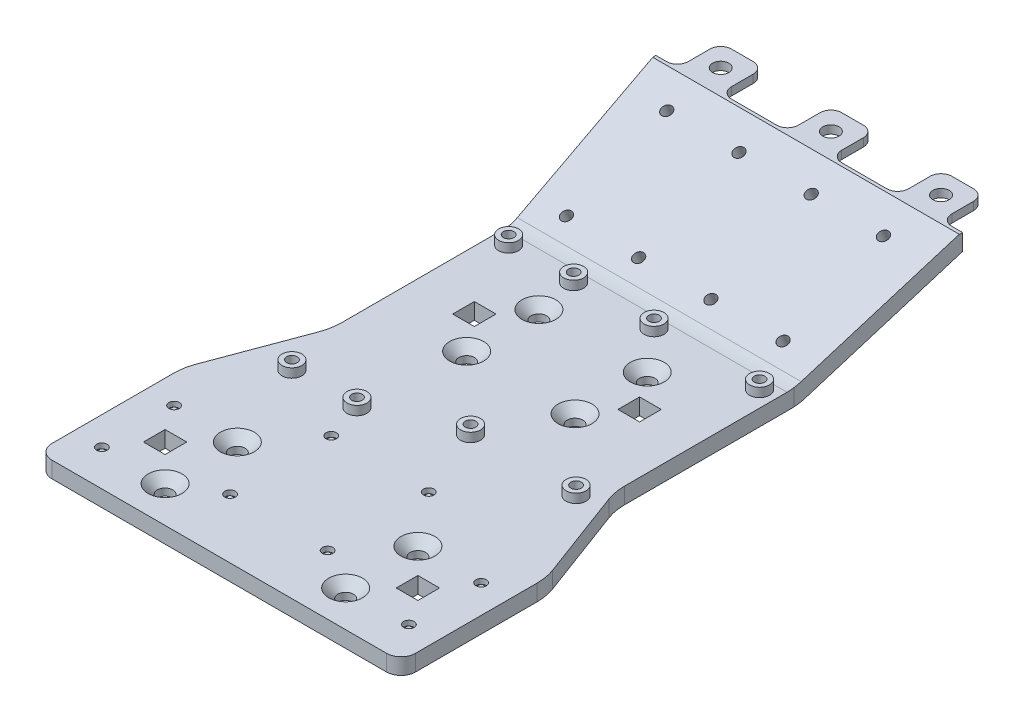
SolidWorks part; units mm, degrees
material "Onyx w/ CF"
ref_plane "Front Plane" through (0, 0, 0) normal (0, 0, 1) x (1, 0, 0)
ref_plane "Top Plane" through (0, 0, 0) normal (0, 1, 0) x (1, 0, 0)
ref_plane "Right Plane" through (0, 0, 0) normal (1, 0, 0) x (0, 0, -1)
sketch "Sketch1" plane through (0, 0, 0) normal (0, 1, 0) x (1, 0, 0)
  line L0 (-39.17, 0) -> (39.17, 0)
  line L3 (-50.325, -79.6) -> (-50.325, -120)
  line L5 (50.325, -120) -> (50.325, -79.6)
  line L8 (-50.325, -120) -> (50.325, -120)
  line L9 (39.17, 0) -> (39.17, -49.7)
  line L10 (-39.17, 0) -> (-39.17, -49.7)
  line L11 (39.17, -49.7) -> (50.325, -79.6)
  line L12 (-50.325, -79.6) -> (-39.17, -49.7)
  point P1 (0, -120)
  point P4 (0, 0)
  dimension "D1" = 78.34
  dimension "D2" = 40.4
  dimension "D3" = 120
  dimension "D4" = 49.7
  dimension "D5" = 100.65
extrude "Boss-Extrude1" add sketch "Sketch1" along normal mid plane 4.5
sketch "Sketch5" plane through (0, 2.25, 0) normal (0, 1, 0) x (1, 0, 0)
  line L3 (-22.875, -26.5) -> (22.875, -26.5) construction
  line L6 (39.17, 0) -> (-39.17, 0) construction
  line L9 (-35, -100) -> (35, -100) construction
  line L19 (-25.875, -23.5) -> (-19.875, -23.5)
  line L20 (-25.875, -23.5) -> (-25.875, -29.5)
  line L21 (-25.875, -29.5) -> (-19.875, -29.5)
  line L22 (-19.875, -23.5) -> (-19.875, -29.5)
  line L23 (-25.875, -23.5) -> (-19.875, -29.5) construction
  line L24 (-25.875, -29.5) -> (-19.875, -23.5) construction
  line L25 (19.875, -23.5) -> (25.875, -23.5)
  line L26 (19.875, -23.5) -> (19.875, -29.5)
  line L27 (19.875, -29.5) -> (25.875, -29.5)
  line L28 (25.875, -23.5) -> (25.875, -29.5)
  line L29 (19.875, -23.5) -> (25.875, -29.5) construction
  line L30 (19.875, -29.5) -> (25.875, -23.5) construction
  line L37 (-50.325, -120) -> (50.325, -120) construction
  line L44 (-38, -97) -> (-32, -97)
  line L45 (-38, -97) -> (-38, -103)
  line L46 (-38, -103) -> (-32, -103)
  line L47 (-32, -97) -> (-32, -103)
  line L48 (-38, -97) -> (-32, -103) construction
  line L49 (-38, -103) -> (-32, -97) construction
  line L50 (32, -97) -> (38, -97)
  line L51 (32, -97) -> (32, -103)
  line L52 (32, -103) -> (38, -103)
  line L53 (38, -97) -> (38, -103)
  line L54 (32, -97) -> (38, -103) construction
  line L55 (32, -103) -> (38, -97) construction
  point P4 (0, -26.5)
  point P5 (0, -100)
  dimension "D1" = 26.5
  dimension "D2" = 45.75
  dimension "D3" = 6
  dimension "D4" = 70
  dimension "D7" = 20
extrude "Cut-Extrude1" cut sketch "Sketch5" against normal through all
hole_wizard "CSK for M4 Flat Head Machine Screw1" positions "Sketch6" profile "Sketch7" countersink size "M4" standard "ANSI Metric" end condition through all
sketch "Sketch6" plane through (0, 2.25, 0) normal (0, -1, 0) x (-1, 0, 0)
  line L1 (-15, -16.5) -> (15, -16.5)
  line L2 (-15, -16.5) -> (-15, -36.5)
  line L3 (-15, -36.5) -> (15, -36.5)
  line L4 (15, -16.5) -> (15, -36.5)
  line L5 (-15, -16.5) -> (15, -36.5) construction
  line L6 (-15, -36.5) -> (15, -16.5) construction
  line L7 (-39.17, 0) -> (39.17, 0) construction
  line L9 (-25, -90) -> (25, -90)
  line L10 (-25, -90) -> (-25, -110)
  line L11 (-25, -110) -> (25, -110)
  line L12 (25, -90) -> (25, -110)
  line L13 (-25, -90) -> (25, -110) construction
  line L14 (-25, -110) -> (25, -90) construction
  line L15 (50.325, -120) -> (-50.325, -120) construction
  point P0 (-15, -16.5)
  point P3 (15, -16.5)
  point P6 (15, -36.5)
  point P8 (-15, -36.5)
  point P49 (0, -36.5)
  point P66 (25, -110)
  point P69 (-25, -90)
  point P70 (-25, -110)
  point P71 (25, -90)
  point P96 (0, -90)
  dimension "D1" = 16.5
  dimension "D2" = 20
  dimension "D3" = 30
  dimension "D4" = 20
  dimension "D5" = 50
  dimension "D6" = 10
sketch "Sketch7" plane through (15, 2.25, 16.5) normal (1, 0, 0) x (0, 0, 1)
  line L0 (0, 0) -> (0, 4.5)
  line L1 (0, 4.5) -> (2.15, 4.5)
  line L2 (2.15, 4.5) -> (2.15, 2.55)
  line L3 (2.15, 2.55) -> (4.7, 0)
  line L5 (4.7, 0) -> (0, 0)
  line L6 (-2.15, 2.55) -> (-4.7, 0) construction
  line L11 (0, -6.35) -> (0, 107.95) construction
  dimension "Thru Hole Dia." = 4.3
  dimension "Thru Hole Depth" = 4.5
  dimension "Near C'Sink Dia." = 9.4
  dimension "Near C'Sink Angle" = 90
fillet "Fillet2" radius 4 2 edges at (-50.325, 0, 120) (50.325, 0, 120)
fillet "Fillet3" radius 15 4 edges at (50.325, 0, 79.6) (39.17, 0, 49.7) (-50.325, 0, 79.6) (-39.17, 0, 49.7)
sketch "Sketch18" plane through (0, 0, 0) normal (1, 0, 0) x (0, 0, -1)
  line L0 (0, 2.25) -> (42.4584, 19.55)
  line L1 (42.4584, 19.55) -> (43.34, 19.55)
  line L2 (43.34, 19.55) -> (43.34, 15.05)
  line L3 (43.34, 15.05) -> (0.8816, -2.25)
  line L4 (0.8816, -2.25) -> (0, -2.25)
  line L5 (0, 2.25) -> (0, -2.25) construction
  line L6 (0, 2.25) -> (0, -2.25)
  dimension "D1" = 43.34
  dimension "D2" = 17.3
  dimension "D3" = 4.5
extrude "Boss-Extrude2" add sketch "Sketch18" against normal mid plane 85
sketch "Sketch21" plane through (0, -2.25, 0) normal (0, -1, 0) x (1, 0, 0)
  line L0 (39.17, 0) -> (42.5, -43.34)
  line L1 (42.5, -43.34) -> (42.5, 0)
  line L2 (42.5, 0) -> (39.17, 0)
  line L3 (39.17, 0) -> (42.5, 0) construction
  line L4 (0, -11.99) -> (0, 11.99) construction
  line L5 (-42.5, 0) -> (-39.17, 0)
  line L6 (-42.5, -43.34) -> (-42.5, 0)
  line L7 (-39.17, 0) -> (-42.5, -43.34)
extrude "Cut-Extrude5" cut sketch "Sketch21" against normal through all
fillet "Fillet5" radius 10 2 edges at (0, 2.25, 0) (0, -2.25, -0.8816)
sketch "Sketch22" plane through (0, 19.55, 0) normal (0, 1, 0) x (1, 0, 0)
  line L0 (-42.5, 43.34) -> (42.5, 43.34) construction
  line L1 (-36.5, 43.34) -> (-24.5, 43.34)
  line L2 (-36.5, 43.34) -> (-36.5, 55.34)
  line L3 (-36.5, 55.34) -> (-24.5, 55.34)
  line L4 (-24.5, 43.34) -> (-24.5, 55.34)
  line L5 (-32.5, 49.34) -> (-36.5, 49.34) construction
  line L6 (6, 43.34) -> (-6, 43.34)
  line L7 (6, 43.34) -> (6, 55.34)
  line L8 (6, 55.34) -> (-6, 55.34)
  line L9 (-6, 43.34) -> (-6, 55.34)
  line L10 (6, 43.34) -> (-6, 55.34) construction
  line L11 (6, 55.34) -> (-6, 43.34) construction
  line L12 (-30.5, 51.34) -> (-30.5, 55.34) construction
  line L13 (0, -11.99) -> (0, 11.99) construction
  line L14 (36.5, 55.34) -> (24.5, 55.34)
  line L15 (24.5, 43.34) -> (24.5, 55.34)
  line L16 (36.5, 43.34) -> (24.5, 43.34)
  line L17 (36.5, 43.34) -> (36.5, 55.34)
  circle A0 centre (-30.5, 49.34) radius 2 construction
  point P6 (0, 49.34)
  point P11 (0, 43.34)
  point P12 (-30.5, 55.34)
  point P17 (-24.5, 49.34)
  dimension "D2" = 4
  dimension "D1" = 12
  dimension "D3" = 4
extrude "Boss-Extrude3" add sketch "Sketch22" against normal blind 2.25
fillet "Fillet6" radius 3 12 edges at (-36.5, 18.425, -55.34) (-36.5, 18.425, -43.34) (-24.5, 18.425, -55.34) (-24.5, 18.425, -43.34) (-6, 18.425, -43.34) (-6, 18.425, -55.34) (6, 18.425, -55.34) (6, 18.425, -43.34) (24.5, 18.425, -43.34) (36.5, 18.425, -43.34) (36.5, 18.425, -55.34) (24.5, 18.425, -55.34)
hole_wizard "M4 Clearance Hole1" positions "Sketch23" profile "Sketch24" hole size "M4" standard "ANSI Metric" end condition through all
sketch "Sketch23" plane through (0, 19.55, 0) normal (0, 1, 0) x (1, 0, 0)
  line L0 (-27.5, 55.34) -> (-33.5, 55.34) construction
  line L1 (-24.5, 46.34) -> (-24.5, 52.34) construction
  line L2 (33.5, 55.34) -> (27.5, 55.34) construction
  line L3 (3, 55.34) -> (-3, 55.34) construction
  point P0 (30.5, 49.34)
  point P2 (0, 49.34)
  point P4 (-30.5, 49.34)
  point P9 (-30.5, 55.34)
  point P12 (-24.5, 49.34)
  point P17 (30.5, 55.34)
  point P20 (0, 55.34)
sketch "Sketch24" plane through (30.5, 19.55, -49.34) normal (1, 0, 0) x (0, 0, 1)
  line L0 (0, 0) -> (0, 21.8)
  line L1 (0, 21.8) -> (2.25, 21.8)
  line L2 (2.25, 21.8) -> (2.25, 0)
  line L5 (2.25, 0) -> (0, 0)
  line L11 (0, -6.35) -> (0, 107.95) construction
  dimension "Thru Hole Dia." = 4.5
  dimension "Thru Hole Depth" = 21.8
hole_wizard "M2.5 Clearance Hole2" positions "Sketch29" profile "Sketch30" hole size "M2.5" standard "ANSI Metric" end condition through all
sketch "Sketch29" plane through (0, 1.9296, 0.7862) normal (0, 0.9261, 0.3773) x (1, 0, 0)
  line L3 (0, 46.6967) -> (0, 0) construction
  line L4 (-42.4323, 46.6967) -> (42.4323, 46.6967) construction
  line L6 (9.17, 38.3483) -> (9.17, 8.3483) construction
  point P0 (29.17, 38.3483)
  point P2 (9.17, 38.3483)
  point P4 (-10.83, 38.3483)
  point P6 (-30.83, 38.3483)
  point P11 (29.17, 8.3483)
  point P13 (9.17, 8.3483)
  point P15 (-10.83, 8.3483)
  point P17 (-30.83, 8.3483)
  point P42 (0, 23.3483)
  point P43 (9.17, 23.3483)
  dimension "D1" = 10
  dimension "D2" = 20
  dimension "D3" = 20
  dimension "D4" = 20
  dimension "D5" = 30
sketch "Sketch30" plane through (29.17, 16.3999, -34.7272) normal (1, 0, 0) x (0, -0.3773, 0.9261)
  line L0 (0, 0) -> (0, 25.0492)
  line L1 (0, 25.0492) -> (1.45, 25.0492)
  line L2 (1.45, 25.0492) -> (1.45, 0)
  line L5 (1.45, 0) -> (0, 0)
  line L11 (0, -6.35) -> (0, 107.95) construction
  dimension "Thru Hole Dia." = 2.9
  dimension "Thru Hole Depth" = 25.0492
sketch "Sketch31" plane through (0, 2.25, 0) normal (0, 1, 0) x (1, 0, 0)
  line L0 (39.17, -1.9591) -> (-39.17, -1.9591) construction
  line L1 (1.07, -1.9591) -> (39.17, -1.9591) construction
  line L2 (1.07, -1.9591) -> (1.07, -59.1091) construction
  line L3 (1.07, -59.1091) -> (39.17, -59.1091) construction
  line L4 (39.17, -1.9591) -> (39.17, -59.1091) construction
  line L5 (39.17, -46.993) -> (39.17, -1.9591) construction
  line L6 (34.725, -5.1341) -> (5.515, -5.1341) construction
  line L7 (34.725, -5.1341) -> (34.725, -55.9341) construction
  line L9 (-16.67, -5.2091) -> (-16.67, -65.2091) construction
  line L10 (-16.67, -65.2091) -> (-34.67, -65.2091) construction
  line L11 (-34.67, -65.2091) -> (-34.67, -5.2091) construction
  line L12 (-34.67, -5.2091) -> (-16.67, -5.2091) construction
  line L13 (-39.17, -1.9591) -> (-39.17, -46.993) construction
  circle A0 centre (34.725, -5.1341) radius 2.75
  circle A1 centre (5.515, -5.1341) radius 2.75
  circle A2 centre (5.515, -55.9341) radius 2.75
  circle A3 centre (34.725, -55.9341) radius 2.75
  circle A4 centre (34.725, -5.1341) radius 1.25 construction
  circle A5 centre (-16.67, -5.2091) radius 2.75
  circle A6 centre (-34.67, -5.2091) radius 2.75
  circle A7 centre (-34.67, -65.2091) radius 2.75
  circle A8 centre (-16.67, -65.2091) radius 2.75
  point P16 (20.12, -1.9591)
  point P17 (20.12, -5.1341)
  point P18 (34.725, -30.5341)
  point P19 (39.17, -30.5341)
  dimension "D3" = 3.175
  dimension "D5" = 2.5
  dimension "D6" = 5.5
  dimension "D7" = 4.5
  dimension "D11" = 5.5
  dimension "D1" = 38.1
  dimension "D2" = 57.15
  dimension "D4" = 29.21
  dimension "D8" = 3.25
  dimension "D9" = 60
  dimension "D10" = 18
extrude "Boss-Extrude4" add sketch "Sketch31" along normal blind 2.5
hole_wizard "M2.5 Clearance Hole3" positions "Sketch32" profile "Sketch33" hole size "M2.5" standard "ANSI Metric" end condition through all
sketch "Sketch32" plane through (0, 4.75, 0) normal (0, 1, 0) x (1, 0, 0)
  line L1 (13.5, -75.5) -> (-13.5, -75.5)
  line L2 (13.5, -75.5) -> (13.5, -103.5)
  line L3 (13.5, -103.5) -> (-13.5, -103.5)
  line L4 (-13.5, -75.5) -> (-13.5, -103.5)
  line L5 (-46.325, -120) -> (46.325, -120) construction
  line L6 (42.5, -90) -> (42.5, -110)
  line L8 (-42.5, -90) -> (-42.5, -110)
  line L10 (42.5, -100) -> (-42.5, -100) construction
  circle A0 centre (34.725, -5.1341) radius 2.75 construction
  circle A1 centre (34.725, -55.9341) radius 2.75 construction
  circle A2 centre (5.515, -5.1341) radius 2.75 construction
  circle A3 centre (5.515, -55.9341) radius 2.75 construction
  circle A4 centre (-16.67, -5.2091) radius 2.75 construction
  circle A5 centre (-16.67, -65.2091) radius 2.75 construction
  circle A6 centre (-34.67, -5.2091) radius 2.75 construction
  circle A7 centre (-34.67, -65.2091) radius 2.75 construction
  point P0 (34.725, -5.1341)
  point P2 (34.725, -55.9341)
  point P4 (5.515, -55.9341)
  point P6 (5.515, -5.1341)
  point P8 (-16.67, -5.2091)
  point P10 (-16.67, -65.2091)
  point P12 (-34.67, -65.2091)
  point P14 (-34.67, -5.2091)
  point P42 (13.5, -75.5)
  point P43 (-13.5, -103.5)
  point P46 (13.5, -103.5)
  point P47 (-13.5, -75.5)
  point P71 (0, -75.5)
  point P88 (-42.5, -90)
  point P90 (-42.5, -110)
  point P92 (42.5, -90)
  point P94 (42.5, -110)
  point P109 (0, -100)
  point P110 (0, -103.5)
  dimension "D1" = 16.5
  dimension "D2" = 28
  dimension "D3" = 27
  dimension "D4" = 85
  dimension "D5" = 20
  dimension "D6" = 20
sketch "Sketch33" plane through (34.725, 4.75, 5.1341) normal (1, 0, 0) x (0, 0, 1)
  line L0 (0, 0) -> (0, 7)
  line L1 (0, 7) -> (1.45, 7)
  line L2 (1.45, 7) -> (1.45, 0)
  line L5 (1.45, 0) -> (0, 0)
  line L11 (0, -6.35) -> (0, 107.95) construction
  dimension "Thru Hole Dia." = 2.9
  dimension "Thru Hole Depth" = 7
sketch "Sketch34" plane through (0, 0, 0) normal (0, 1, 0) x (1, 0, 0)
  line L0 (37.5774, -2.2817) -> (37.5774, -7.9865)
  line L1 (8.215, -2.4341) -> (2.815, -2.4341) construction
  line L2 (8.215, -2.4341) -> (8.215, -7.8341) construction
  line L3 (8.215, -7.8341) -> (2.815, -7.8341) construction
  line L4 (2.815, -2.4341) -> (2.815, -7.8341) construction
  line L5 (8.215, -2.4341) -> (2.815, -7.8341) construction
  line L6 (8.215, -7.8341) -> (2.815, -2.4341) construction
  line L7 (8.215, -53.2341) -> (2.815, -53.2341) construction
  line L8 (8.215, -53.2341) -> (8.215, -58.6341) construction
  line L9 (8.215, -58.6341) -> (2.815, -58.6341) construction
  line L10 (2.815, -53.2341) -> (2.815, -58.6341) construction
  line L11 (8.215, -53.2341) -> (2.815, -58.6341) construction
  line L12 (8.215, -58.6341) -> (2.815, -53.2341) construction
  line L13 (37.425, -53.2341) -> (32.025, -53.2341) construction
  line L14 (37.425, -53.2341) -> (37.425, -58.6341) construction
  line L15 (37.425, -58.6341) -> (32.025, -58.6341) construction
  line L16 (32.025, -53.2341) -> (32.025, -58.6341) construction
  line L17 (37.425, -53.2341) -> (32.025, -58.6341) construction
  line L18 (37.425, -58.6341) -> (32.025, -53.2341) construction
  line L19 (37.425, -2.4341) -> (32.025, -2.4341) construction
  line L20 (37.425, -2.4341) -> (37.425, -7.8341) construction
  line L21 (37.425, -7.8341) -> (32.025, -7.8341) construction
  line L22 (32.025, -2.4341) -> (32.025, -7.8341) construction
  line L23 (37.425, -2.4341) -> (32.025, -7.8341) construction
  line L24 (37.425, -7.8341) -> (32.025, -2.4341) construction
  line L25 (-13.97, -2.5091) -> (-19.37, -2.5091) construction
  line L26 (-13.97, -2.5091) -> (-13.97, -7.9091) construction
  line L27 (-13.97, -7.9091) -> (-19.37, -7.9091) construction
  line L28 (-19.37, -2.5091) -> (-19.37, -7.9091) construction
  line L29 (-13.97, -2.5091) -> (-19.37, -7.9091) construction
  line L30 (-13.97, -7.9091) -> (-19.37, -2.5091) construction
  line L31 (-31.97, -2.5091) -> (-37.37, -2.5091) construction
  line L32 (-31.97, -2.5091) -> (-31.97, -7.9091) construction
  line L33 (-31.97, -7.9091) -> (-37.37, -7.9091) construction
  line L34 (-37.37, -2.5091) -> (-37.37, -7.9091) construction
  line L35 (-31.97, -2.5091) -> (-37.37, -7.9091) construction
  line L36 (-31.97, -7.9091) -> (-37.37, -2.5091) construction
  line L37 (-31.97, -62.5091) -> (-37.37, -62.5091) construction
  line L38 (-31.97, -62.5091) -> (-31.97, -67.9091) construction
  line L39 (-31.97, -67.9091) -> (-37.37, -67.9091) construction
  line L40 (-37.37, -62.5091) -> (-37.37, -67.9091) construction
  line L41 (-31.97, -62.5091) -> (-37.37, -67.9091) construction
  line L42 (-31.97, -67.9091) -> (-37.37, -62.5091) construction
  line L43 (-13.97, -62.5091) -> (-19.37, -62.5091) construction
  line L44 (-13.97, -62.5091) -> (-13.97, -67.9091) construction
  line L45 (-13.97, -67.9091) -> (-19.37, -67.9091) construction
  line L46 (-19.37, -62.5091) -> (-19.37, -67.9091) construction
  line L47 (-13.97, -62.5091) -> (-19.37, -67.9091) construction
  line L48 (-13.97, -67.9091) -> (-19.37, -62.5091) construction
  line L49 (37.5774, -7.9865) -> (31.8726, -7.9865)
  line L50 (31.8726, -2.2817) -> (31.8726, -7.9865)
  line L51 (37.5774, -2.2817) -> (31.8726, -2.2817)
  line L52 (31.8726, -53.0817) -> (31.8726, -58.7865)
  line L53 (37.5774, -58.7865) -> (31.8726, -58.7865)
  line L54 (37.5774, -53.0817) -> (37.5774, -58.7865)
  line L55 (37.5774, -53.0817) -> (31.8726, -53.0817)
  line L56 (2.6626, -53.0817) -> (2.6626, -58.7865)
  line L57 (8.3674, -58.7865) -> (2.6626, -58.7865)
  line L58 (8.3674, -53.0817) -> (8.3674, -58.7865)
  line L59 (8.3674, -53.0817) -> (2.6626, -53.0817)
  line L60 (2.6626, -2.2817) -> (2.6626, -7.9865)
  line L61 (8.3674, -7.9865) -> (2.6626, -7.9865)
  line L62 (8.3674, -2.2817) -> (8.3674, -7.9865)
  line L63 (8.3674, -2.2817) -> (2.6626, -2.2817)
  line L64 (-19.5224, -2.3567) -> (-19.5224, -8.0615)
  line L65 (-13.8176, -8.0615) -> (-19.5224, -8.0615)
  line L66 (-13.8176, -2.3567) -> (-13.8176, -8.0615)
  line L67 (-13.8176, -2.3567) -> (-19.5224, -2.3567)
  line L68 (-31.8176, -2.3567) -> (-31.8176, -8.0615)
  line L69 (-31.8176, -8.0615) -> (-37.5224, -8.0615)
  line L70 (-37.5224, -2.3567) -> (-37.5224, -8.0615)
  line L71 (-31.8176, -2.3567) -> (-37.5224, -2.3567)
  line L72 (-19.5224, -62.3567) -> (-19.5224, -68.0615)
  line L73 (-13.8176, -68.0615) -> (-19.5224, -68.0615)
  line L74 (-13.8176, -62.3567) -> (-13.8176, -68.0615)
  line L75 (-13.8176, -62.3567) -> (-19.5224, -62.3567)
  line L76 (-31.8176, -62.3567) -> (-31.8176, -68.0615)
  line L77 (-31.8176, -68.0615) -> (-37.5224, -68.0615)
  line L78 (-37.5224, -62.3567) -> (-37.5224, -68.0615)
  line L79 (-31.8176, -62.3567) -> (-37.5224, -62.3567)
  line L80 (16.3524, -78.3524) -> (10.6476, -78.3524)
  line L81 (16.2, -72.8) -> (10.8, -72.8) construction
  line L82 (16.2, -72.8) -> (16.2, -78.2) construction
  line L83 (16.2, -78.2) -> (10.8, -78.2) construction
  line L84 (10.8, -72.8) -> (10.8, -78.2) construction
  line L85 (16.2, -72.8) -> (10.8, -78.2) construction
  line L86 (16.2, -78.2) -> (10.8, -72.8) construction
  line L87 (16.2, -100.8) -> (10.8, -100.8) construction
  line L88 (16.2, -100.8) -> (16.2, -106.2) construction
  line L89 (16.2, -106.2) -> (10.8, -106.2) construction
  line L90 (10.8, -100.8) -> (10.8, -106.2) construction
  line L91 (16.2, -100.8) -> (10.8, -106.2) construction
  line L92 (16.2, -106.2) -> (10.8, -100.8) construction
  line L93 (-10.8, -100.8) -> (-16.2, -100.8) construction
  line L94 (-10.8, -100.8) -> (-10.8, -106.2) construction
  line L95 (-10.8, -106.2) -> (-16.2, -106.2) construction
  line L96 (-16.2, -100.8) -> (-16.2, -106.2) construction
  line L97 (-10.8, -100.8) -> (-16.2, -106.2) construction
  line L98 (-10.8, -106.2) -> (-16.2, -100.8) construction
  line L99 (-10.8, -72.8) -> (-16.2, -72.8) construction
  line L100 (-10.8, -72.8) -> (-10.8, -78.2) construction
  line L101 (-10.8, -78.2) -> (-16.2, -78.2) construction
  line L102 (-16.2, -72.8) -> (-16.2, -78.2) construction
  line L103 (-10.8, -72.8) -> (-16.2, -78.2) construction
  line L104 (-10.8, -78.2) -> (-16.2, -72.8) construction
  line L105 (10.6476, -72.6476) -> (10.6476, -78.3524)
  line L106 (16.3524, -72.6476) -> (10.6476, -72.6476)
  line L107 (16.3524, -72.6476) -> (16.3524, -78.3524)
  line L108 (16.3524, -100.6476) -> (10.6476, -100.6476)
  line L109 (10.6476, -100.6476) -> (10.6476, -106.3524)
  line L110 (16.3524, -106.3524) -> (10.6476, -106.3524)
  line L111 (16.3524, -100.6476) -> (16.3524, -106.3524)
  line L112 (-10.6476, -78.3524) -> (-16.3524, -78.3524)
  line L113 (-16.3524, -72.6476) -> (-16.3524, -78.3524)
  line L114 (-10.6476, -72.6476) -> (-16.3524, -72.6476)
  line L115 (-10.6476, -72.6476) -> (-10.6476, -78.3524)
  line L116 (-10.6476, -100.6476) -> (-16.3524, -100.6476)
  line L117 (-16.3524, -100.6476) -> (-16.3524, -106.3524)
  line L118 (-10.6476, -106.3524) -> (-16.3524, -106.3524)
  line L119 (-10.6476, -100.6476) -> (-10.6476, -106.3524)
  line L120 (39.6476, -87.1476) -> (39.6476, -92.8524)
  line L121 (45.2, -87.3) -> (39.8, -87.3) construction
  line L122 (45.2, -87.3) -> (45.2, -92.7) construction
  line L123 (45.2, -92.7) -> (39.8, -92.7) construction
  line L124 (39.8, -87.3) -> (39.8, -92.7) construction
  line L125 (45.2, -87.3) -> (39.8, -92.7) construction
  line L126 (45.2, -92.7) -> (39.8, -87.3) construction
  line L127 (45.2, -107.3) -> (39.8, -107.3) construction
  line L128 (45.2, -107.3) -> (45.2, -112.7) construction
  line L129 (45.2, -112.7) -> (39.8, -112.7) construction
  line L130 (39.8, -107.3) -> (39.8, -112.7) construction
  line L131 (45.2, -107.3) -> (39.8, -112.7) construction
  line L132 (45.2, -112.7) -> (39.8, -107.3) construction
  line L133 (-39.8, -87.3) -> (-45.2, -87.3) construction
  line L134 (-39.8, -87.3) -> (-39.8, -92.7) construction
  line L135 (-39.8, -92.7) -> (-45.2, -92.7) construction
  line L136 (-45.2, -87.3) -> (-45.2, -92.7) construction
  line L137 (-39.8, -87.3) -> (-45.2, -92.7) construction
  line L138 (-39.8, -92.7) -> (-45.2, -87.3) construction
  line L139 (-39.8, -107.3) -> (-45.2, -107.3) construction
  line L140 (-39.8, -107.3) -> (-39.8, -112.7) construction
  line L141 (-39.8, -112.7) -> (-45.2, -112.7) construction
  line L142 (-45.2, -107.3) -> (-45.2, -112.7) construction
  line L143 (-39.8, -107.3) -> (-45.2, -112.7) construction
  line L144 (-39.8, -112.7) -> (-45.2, -107.3) construction
  line L145 (45.3524, -92.8524) -> (39.6476, -92.8524)
  line L146 (45.3524, -87.1476) -> (45.3524, -92.8524)
  line L147 (45.3524, -87.1476) -> (39.6476, -87.1476)
  line L148 (45.3524, -107.1476) -> (39.6476, -107.1476)
  line L149 (39.6476, -107.1476) -> (39.6476, -112.8524)
  line L150 (45.3524, -112.8524) -> (39.6476, -112.8524)
  line L151 (45.3524, -107.1476) -> (45.3524, -112.8524)
  line L152 (-45.3524, -87.1476) -> (-45.3524, -92.8524)
  line L153 (-39.6476, -92.8524) -> (-45.3524, -92.8524)
  line L154 (-39.6476, -87.1476) -> (-39.6476, -92.8524)
  line L155 (-39.6476, -87.1476) -> (-45.3524, -87.1476)
  line L156 (-39.6476, -107.1476) -> (-45.3524, -107.1476)
  line L157 (-45.3524, -107.1476) -> (-45.3524, -112.8524)
  line L158 (-39.6476, -112.8524) -> (-45.3524, -112.8524)
  line L159 (-39.6476, -107.1476) -> (-39.6476, -112.8524)
  circle A0 centre (34.725, -5.1341) radius 1.45 construction
  circle A1 centre (34.725, -55.9341) radius 2.75 construction
  circle A2 centre (5.515, -5.1341) radius 2.75 construction
  circle A3 centre (5.515, -55.9341) radius 2.75 construction
  circle A4 centre (-16.67, -5.2091) radius 2.75 construction
  circle A5 centre (-16.67, -65.2091) radius 2.75 construction
  circle A6 centre (-34.67, -5.2091) radius 2.75 construction
  circle A7 centre (-34.67, -65.2091) radius 2.75 construction
  circle A8 centre (-13.5, -75.5) radius 1.45 construction
  circle A9 centre (13.5, -75.5) radius 1.45 construction
  circle A10 centre (13.5, -103.5) radius 1.45 construction
  circle A11 centre (-13.5, -103.5) radius 1.45 construction
  circle A13 centre (-42.5, -90) radius 1.45 construction
  circle A14 centre (-42.5, -110) radius 1.45 construction
  circle A15 centre (42.5, -90) radius 1.45 construction
  circle A16 centre (42.5, -110) radius 1.45 construction
  point P0 (5.515, -5.1341)
  point P5 (5.515, -55.9341)
  point P10 (34.725, -55.9341)
  point P15 (34.725, -5.1341)
  point P20 (-16.67, -5.2091)
  point P25 (-34.67, -5.2091)
  point P30 (-34.67, -65.2091)
  point P35 (-16.67, -65.2091)
  point P42 (13.5, -103.5)
  point P55 (-13.5, -103.5)
  point P98 (13.5, -75.5)
  point P103 (-13.5, -75.5)
  point P110 (42.5, -90)
  point P121 (42.5, -110)
  point P142 (-42.5, -90)
  point P147 (-42.5, -110)
  dimension "D1" = 5.4
  dimension "D2" = 0.1524
  dimension "D3" = 0.1524
  dimension "D4" = 0.1524
extrude "Cut-Extrude6" cut sketch "Sketch34" against normal mid plane 1.7
